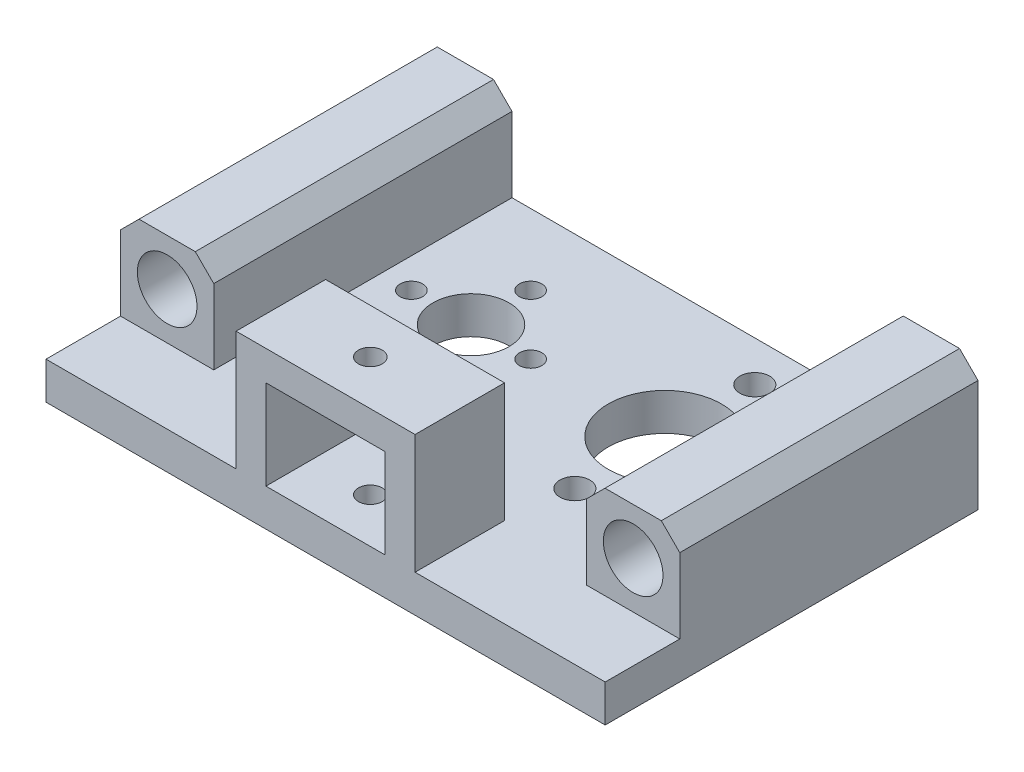
SolidWorks part; units mm, degrees
ref_plane "Front Plane" through (0, 0, 0) normal (0, 0, 1) x (1, 0, 0)
ref_plane "Top Plane" through (0, 0, 0) normal (0, 1, 0) x (1, 0, 0)
ref_plane "Right Plane" through (0, 0, 0) normal (1, 0, 0) x (0, 0, -1)
sketch "Sketch1" plane through (0, 0, 0) normal (0, 1, 0) x (1, 0, 0)
  line L0 (0, 32.5) -> (75, 32.5) construction
  line L1 (0, 0) -> (75, 0)
  line L2 (0, 0) -> (0, 50)
  line L3 (0, 50) -> (75, 50)
  line L4 (75, 0) -> (75, 50)
  line L5 (37.5, 50) -> (37.5, 0) construction
  line L6 (37.5, 32.5) -> (24.5, 32.5) construction
  line L7 (37.5, 32.5) -> (50.5, 32.5) construction
  circle A0 centre (24.5, 32.5) radius 5.1
  circle A1 centre (50.5, 32.5) radius 7.6
  point P13 (0, 0)
  point P15 (37.5, 32.5)
  dimension "D2" = 10.2
  dimension "D6" = 15.2
  dimension "D1" = 26
  dimension "D3" = 75
  dimension "D4" = 50
  dimension "D5" = 17.5
extrude "Boss-Extrude1" add sketch "Sketch1" along normal blind 5
sketch "Sketch2" plane through (0, 5, 0) normal (0, 1, 0) x (1, 0, 0)
  line L4 (0, 50) -> (12.5, 50)
  line L5 (0, 50) -> (0, 10)
  line L6 (0, 10) -> (12.5, 10)
  line L7 (12.5, 50) -> (12.5, 10)
  line L8 (75, 50) -> (62.5, 50)
  line L9 (75, 50) -> (75, 10)
  line L10 (75, 10) -> (62.5, 10)
  line L11 (62.5, 50) -> (62.5, 10)
  dimension "D1" = 40
  dimension "D3" = 12.5
extrude "Boss-Extrude2" add sketch "Sketch2" along normal blind 12.5
sketch "Sketch3" plane through (0, 0, -50) normal (0, 0, -1) x (-1, 0, 0)
  line L0 (-37.5, 0) -> (-37.5, 50000) construction
  line L1 (-75, 0) -> (0, 0) construction
  line L2 (-62.5, 5) -> (-12.5, 5) construction
  line L3 (-72.5251, 17.5) -> (-75, 17.5)
  line L4 (-75, 17.5) -> (-62.5, 17.5) construction
  line L5 (-75, 17.5) -> (-75, 15.0251)
  line L6 (-75, 17.5) -> (-75, 0) construction
  line L7 (-75, 15.0251) -> (-72.5251, 17.5)
  line L8 (-62.5, 17.5) -> (-64.9749, 17.5)
  line L9 (-64.9749, 17.5) -> (-62.5, 15.0251)
  line L10 (-62.5, 17.5) -> (-62.5, 5) construction
  line L11 (-62.5, 15.0251) -> (-62.5, 17.5)
  line L12 (-68.75, 17.5) -> (-68.75, 0) construction
  line L13 (-62.5, 11.25) -> (-75, 11.25) construction
  line L14 (-12.5, 11.25) -> (0, 11.25) construction
  line L15 (-6.25, 17.5) -> (-6.25, 0) construction
  line L16 (-12.5, 15.0251) -> (-12.5, 17.5)
  line L17 (-10.0251, 17.5) -> (-12.5, 15.0251)
  line L18 (-12.5, 17.5) -> (-10.0251, 17.5)
  line L19 (0, 15.0251) -> (-2.4749, 17.5)
  line L20 (0, 17.5) -> (0, 15.0251)
  line L21 (-2.4749, 17.5) -> (0, 17.5)
  circle A0 centre (-68.75, 11.25) radius 4
  circle A1 centre (-6.25, 11.25) radius 4
  point P4 (-37.5, 0)
  point P7 (-37.5, 5)
  dimension "D1" = 8
  dimension "D2" = 3.5
extrude "Cut-Extrude1" cut sketch "Sketch3" against normal through all
sketch "Sketch4" plane through (0, 5, 0) normal (0, 1, 0) x (1, 0, 0)
  line L0 (37.5, 0) -> (37.5, 50) construction
  line L1 (0, 0) -> (75, 0) construction
  line L2 (62.5, 50) -> (12.5, 50) construction
  line L4 (45.5, 0) -> (49.5, 0)
  line L5 (45.5, 0) -> (45.5, 12)
  line L6 (45.5, 12) -> (49.5, 12)
  line L7 (49.5, 0) -> (49.5, 12)
  line L8 (25.5, 0) -> (29.5, 0)
  line L9 (25.5, 0) -> (25.5, 12)
  line L10 (25.5, 12) -> (29.5, 12)
  line L11 (29.5, 0) -> (29.5, 12)
  point P14 (49.7942, 12.8934)
  dimension "D1" = 4
  dimension "D3" = 8
  dimension "D4" = 8
  dimension "D5" = 12
extrude "Boss-Extrude3" add sketch "Sketch4" along normal blind 12
sketch "Sketch5" plane through (0, 0, -12) normal (0, 0, -1) x (-1, 0, 0)
  line L0 (-49.5, 5) -> (-45.5, 5) construction
  line L1 (-49.5, 17) -> (-25.5, 17)
  line L2 (-49.5, 17) -> (-49.5, 21)
  line L3 (-49.5, 21) -> (-25.5, 21)
  line L4 (-25.5, 17) -> (-25.5, 21)
  point P5 (0, 0)
extrude "Boss-Extrude4" add sketch "Sketch5" against normal up to surface (12 mm away) up to face at (37.5, 8.1667, 0)
sketch "Sketch6" plane through (0, 21, 0) normal (0, 1, 0) x (1, 0, 0)
  line L0 (49.5, 6) -> (25.5, 6) construction
  line L1 (49.5, 0) -> (49.5, 12) construction
  line L2 (25.5, 0) -> (25.5, 12) construction
  line L3 (37.5, 0) -> (37.5, 12) construction
  line L4 (49.5, 0) -> (25.5, 0) construction
  line L5 (25.5, 12) -> (49.5, 12) construction
  circle A0 centre (37.5, 6) radius 1.6
  dimension "D1" = 3.2
extrude "Cut-Extrude2" cut sketch "Sketch6" against normal through all
sketch "Sketch7" plane through (0, 5, 0) normal (0, 1, 0) x (1, 0, 0)
  line L0 (50.5, 24.9) -> (50.5, 40.1) construction
  line L1 (24.5, 37.6) -> (24.5, 27.4) construction
  line L2 (29.6, 32.5) -> (19.4, 32.5) construction
  circle A1 centre (50.5, 20.43) radius 2
  circle A2 centre (50.5, 44.565) radius 2
  circle A3 centre (50.5, 32.5) radius 7.6 construction
  circle A4 centre (24.5, 32.5) radius 5.1 construction
  circle A6 centre (24.5, 40.5) radius 1.5
  circle A7 centre (16.5, 32.5) radius 1.5
  circle A8 centre (32.5, 32.5) radius 1.5
  circle A9 centre (24.5, 24.5) radius 1.5
  point P10 (50.5, 32.5)
  point P20 (24.5, 32.5)
  point P23 (21.9615, 40.1)
  point P24 (0, 0)
  dimension "D3" = 4
  dimension "D6" = 3
  dimension "D1" = 12.065
  dimension "D2" = 12.07
  dimension "D4" = 8
  dimension "D5" = 8
extrude "Cut-Extrude4" cut sketch "Sketch7" against normal through all
equation "\"8mm hole\" = 8mm"
equation "\"22mm hole\"= 22mm"
